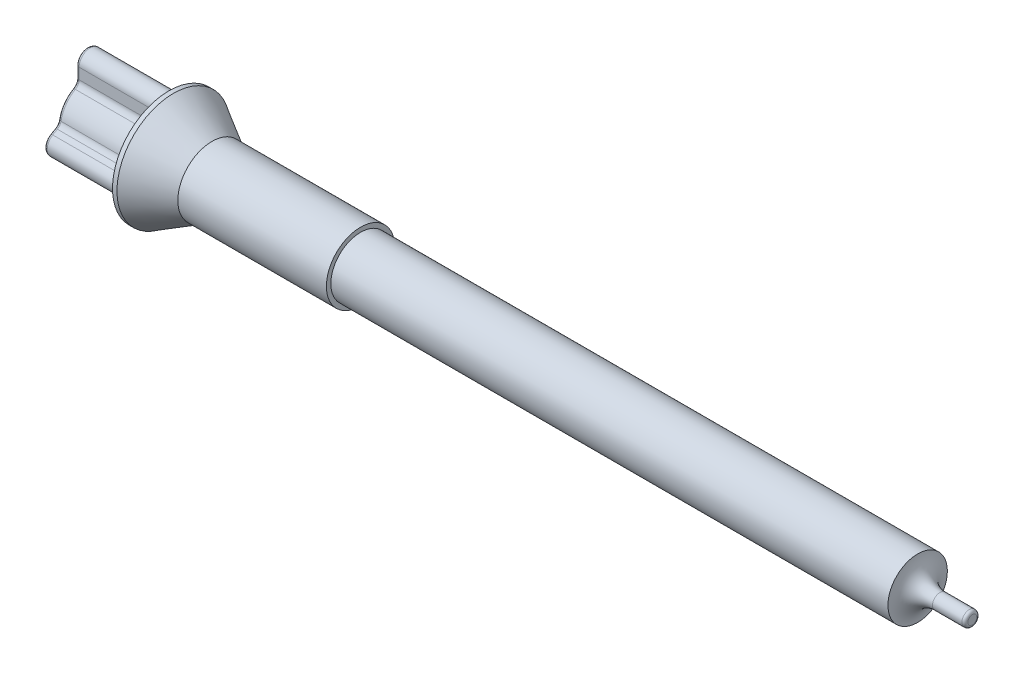
SolidWorks part; units mm, degrees
ref_plane "Front Plane" through (0, 0, 0) normal (0, 0, 1) x (1, 0, 0)
ref_plane "Top Plane" through (0, 0, 0) normal (0, 1, 0) x (1, 0, 0)
ref_plane "Right Plane" through (0, 0, 0) normal (1, 0, 0) x (0, 0, -1)
sketch "Sketch1" plane through (0, 0, 0) normal (0, 0, 1) x (1, 0, 0)
  line L0 (0, 0) -> (0, 1)
  line L1 (0, 1) -> (2.75, 1)
  line L2 (2.75, 1) -> (2.75, 1.9)
  line L3 (2.75, 1.9) -> (2.9, 1.9)
  line L4 (2.9, 1.9) -> (4.199, 1.15)
  line L5 (4.199, 1.15) -> (9.199, 1.15)
  line L6 (9.199, 1.15) -> (9.199, 1)
  line L7 (9.199, 1) -> (27.949, 1)
  line L8 (27.949, 1) -> (27.949, 0)
  line L9 (27.949, 0) -> (0, 0)
  dimension "D1" = 18.75
  dimension "D2" = 5
  dimension "D3" = 0.15
  dimension "D4" = 2.75
  dimension "D5" = 1
  dimension "D6" = 1
  dimension "D7" = 0.9
  dimension "D8" = 1.15
  dimension "D9" = 150
revolve "Revolve1" add sketch "Sketch1" angle 360 about L9
sketch "Sketch2" plane through (0, 0, 0) normal (-1, 0, 0) x (0, 0, 1)
  line L1 (-0.375, 1.45) -> (0.375, 1.45) construction
  line L2 (-0.375, 1.45) -> (-0.375, 0)
  line L3 (-0.375, 0) -> (0.375, 0)
  line L4 (0.375, 1.45) -> (0.375, 0)
  line L5 (-0.375, 1.45) -> (0.375, 0) construction
  line L6 (-0.375, 0) -> (0.375, 1.45) construction
  arc A0 (-0.375, 1.45) -> (0.375, 1.45) centre (0, 1.45) cw
  point P0 (0, 0.725)
  point P5 (0, 0)
  dimension "D1" = 0.75
  dimension "D2" = 1.45
extrude "Boss-Extrude1" add sketch "Sketch2" against normal up to next
pattern_circular "CirPattern1" count 3 over 360 about axis through (0, 0.2115, 0) along (1, 0, 0) of "Boss-Extrude1"
fillet "Fillet1" radius 0.25 9 edges at (2.75, -1, 0) (1.375, -0.6568, 0.754) (1.375, -0.6568, -0.754) (2.75, 0.5871, -0.8095) (1.375, 0.0686, -0.9976) (1.375, 0.927, -0.375) (1.375, 0.0686, 0.9976) (2.75, 0.5871, 0.8095) (1.375, 0.927, 0.375)
sketch "Sketch3" plane through (27.949, 0, 0) normal (1, 0, 0) x (0, 0, -1)
  circle A0 centre (0, 0) radius 0.25
  dimension "D1" = 0.5
extrude "Boss-Extrude2" add sketch "Sketch3" along normal blind 1.84
fillet "Fillet2" radius 0.75 1 edges at (27.949, 0, -0.25)
fillet "Fillet3" radius 0.1 17 edges at (29.789, 0, -0.25) (0, 1.2663, -0.375) (0, 1.825, 0) (0, -0.5855, -1.4027) (0, -0.0382, 1.1825) (0, -1, 0) (0, -0.5855, 1.4027) (0, 0.5756, -0.8177) (0, -0.0382, -1.1825) (0, 0.5756, 0.8177) (0, 1.2663, 0.375) (0, -0.7181, 0.7649) (0, -0.7181, -0.7649) (0, 0.0792, -1.0255) (0, 0.9575, -0.4085) (0, 0.0792, 1.0255) (0, 0.9575, 0.4085)
